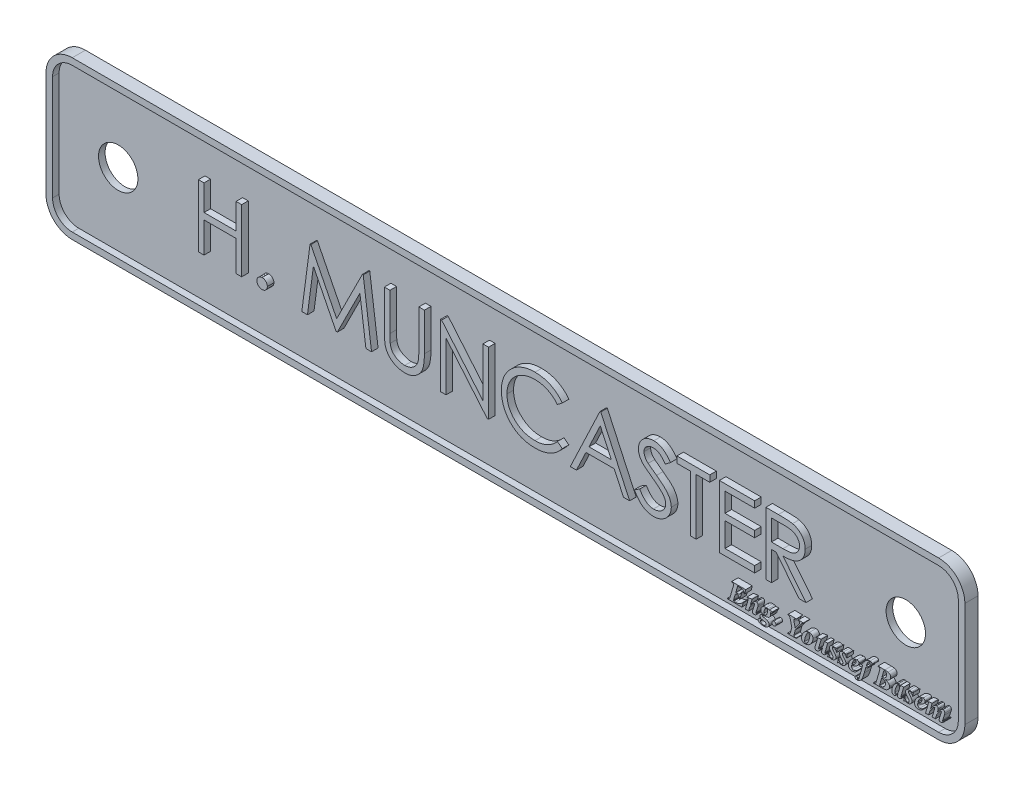
SolidWorks part; units mm, degrees
ref_plane "Front Plane" through (0, 0, 0) normal (0, 0, 1) x (1, 0, 0)
ref_plane "Top Plane" through (0, 0, 0) normal (0, 1, 0) x (1, 0, 0)
ref_plane "Right Plane" through (0, 0, 0) normal (1, 0, 0) x (0, 0, -1)
sketch "Sketch1" plane through (0, 0, 0) normal (0, 0, 1) x (1, 0, 0)
  line L0 (-33, 5.5) -> (33, 5.5)
  line L1 (-33, -6) -> (33, -6)
  line L2 (-35, -4) -> (-35, 4)
  line L3 (-33, 6) -> (33, 6)
  line L4 (35, -4) -> (35, 4)
  line L5 (-35, -6) -> (35, 6) construction
  line L6 (-35, 6) -> (35, -6) construction
  line L7 (34.5, -4) -> (34.5, 4)
  line L8 (-33, -5.5) -> (33, -5.5)
  line L9 (-34.5, -4) -> (-34.5, 4)
  arc A0 (-33, -6) -> (-35, -4) centre (-33, -4) cw
  arc A1 (33, -6) -> (35, -4) centre (33, -4) ccw
  arc A2 (33, 6) -> (35, 4) centre (33, 4) cw
  arc A3 (-35, 4) -> (-33, 6) centre (-33, 4) cw
  arc A4 (-34.5, 4) -> (-33, 5.5) centre (-33, 4) cw
  arc A5 (33, 5.5) -> (34.5, 4) centre (33, 4) cw
  arc A6 (33, -5.5) -> (34.5, -4) centre (33, -4) ccw
  arc A7 (-33, -5.5) -> (-34.5, -4) centre (-33, -4) cw
  circle A8 centre (30, 0) radius 1.5
  circle A9 centre (-30, 0) radius 1.5
  point P0 (0, 0)
  dimension "D3" = 2
  dimension "D4" = 0.5
  dimension "D5" = 4.5
  dimension "D7" = 3
  dimension "D1" = 70
  dimension "D2" = 12
  dimension "D6" = 4.5
extrude "Boss-Extrude1" add sketch "Sketch1" along normal blind 1 contours A3 L2 A0 L1 A1 L4 A2 L3 L8 A7 L9 A4 L0 A5 L7 A6 region at (-34.364, -5.364, 0)
extrude "Boss-Extrude2" add sketch "Sketch1<3>" along normal blind 0.5 contours A7 L8 A6 L7 A5 L0 A4 L9 A9 A8 region at (0, 0, 0)
sketch "Sketch1<3>" plane through (0, 0, 0) normal (0, 0, 1) x (1, 0, 0) same geometry as "Sketch1"
sketch "Sketch3" plane through (0, 0, 0.5) normal (0, 0, 1) x (1, 0, 0)
  line L0 (-24, -2) -> (24.0841, -2) construction
  line L1 (-33, -5.5) -> (33, -5.5) construction
  line L2 (-34.5, -4) -> (-34.5, 4) construction
  line L3 (-24, 3.0277) -> (24.0841, 3.0277) construction
  line L5 (16.9607, -4.7397) -> (37.5353, -4.7397) construction
  text T0 "H. MUNCASTER" font "Century Gothic" height in points 18
  text T1 "Eng. Youssef Basem" font "Times New Roman" height 1.3
  point P9 (20.72, -4.6342)
  point P10 (18.3168, -4.5666)
  point P11 (0, 0)
  point P12 (18.2593, -4.9695)
  point P13 (0, 0)
  point P17 (17.9715, -4.6434)
  point P18 (17.3192, -4.6626)
  point P19 (16.3791, -4.6818)
  point P20 (16.9607, -4.7397)
  dimension "D1" = 3.5
  dimension "D2" = 10.5
extrude "Boss-Extrude4" add sketch "Sketch3" along normal blind 0.5 separate body
